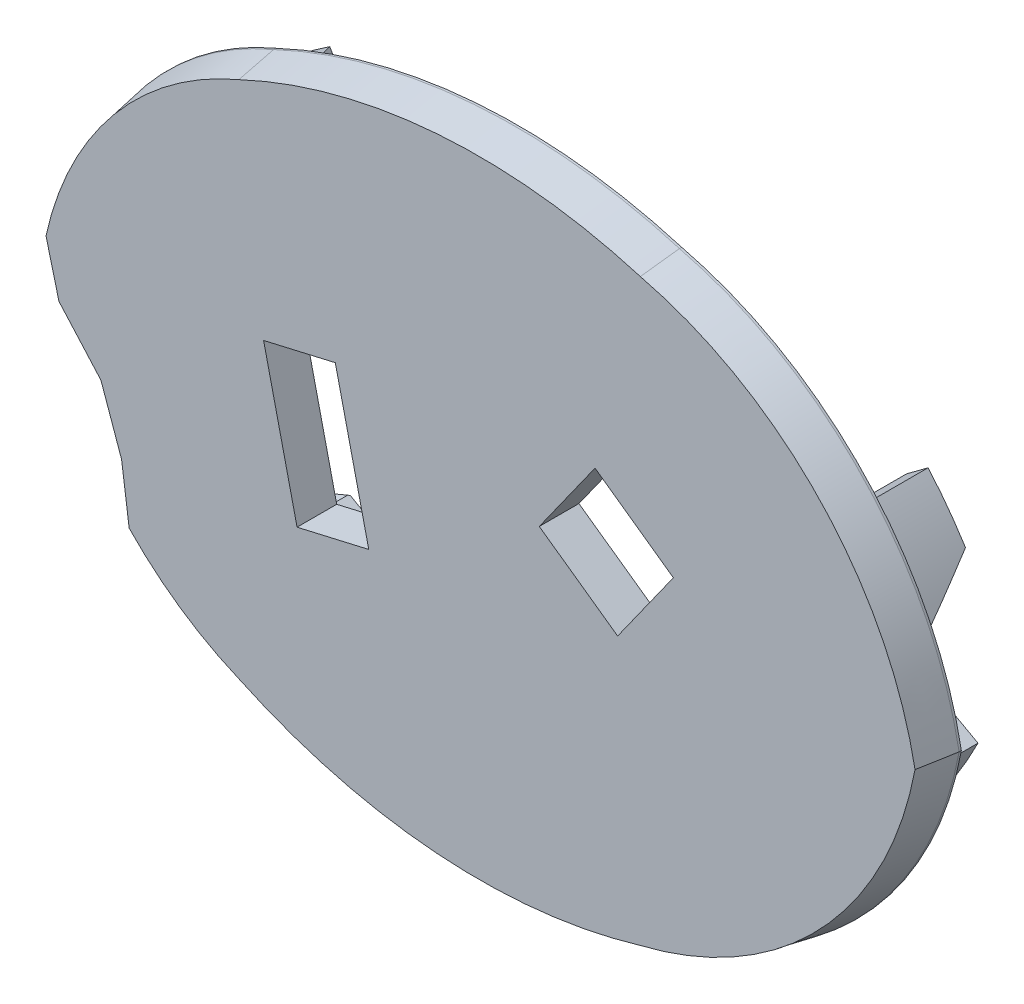
SolidWorks part; units mm, degrees
ref_plane "Ön Düzlem" through (0, 0, 0) normal (0, 0, 1) x (1, 0, 0)
ref_plane "Üst Düzlem" through (0, 0, 0) normal (0, 1, 0) x (1, 0, 0)
ref_plane "Sağ Düzlem" through (0, 0, 0) normal (1, 0, 0) x (0, 0, -1)
sketch "Çizim1" plane through (0, 0, 0) normal (0, 0, 1) x (1, 0, 0)
  line L2 (-58.677, -17.6893) -> (-56.8396, -24.8216)
  line L3 (-56.8396, -24.8216) -> (-51.1973, -31.1692)
  line L8 (-51.1973, -31.1692) -> (-48.5261, -38.7135)
  line L9 (-48.5261, -38.7135) -> (-47.4867, -46.3583)
  arc A1 (59.3086, -21.378) -> (21.9184, 18.1981) centre (10.0775, -30.4393) ccw
  arc A2 (21.9184, 18.1981) -> (-32.3459, 14.1122) centre (0.1322, -54.8435) ccw
  arc A5 (-32.3459, 14.1122) -> (-58.677, -17.6893) centre (-14.9778, -27.0699) ccw
  arc A6 (-32.3459, -56.8682) -> (-47.4867, -46.3583) centre (-14.9778, -15.6861) cw
  arc A9 (21.9184, -60.9541) -> (-32.3459, -56.8682) centre (0.1322, 12.0875) cw
  arc A10 (59.3086, -21.378) -> (21.9184, -60.9541) centre (10.0775, -12.3167) cw
extrude "Yükseklik-Ekstrüzyon1" add sketch "Çizim1" along normal blind 5.3
chamfer "Pah1" distance 5 angle 10 10 edges at (46.4645, 3.9379, 5.3) (46.4645, -46.6939, 5.3) (-5.5908, -63.9188, 5.3) (-40.464, -52.4022, 5.3) (-48.0064, -42.5359, 5.3) (-49.8617, -34.9414, 5.3) (-54.0184, -27.9954, 5.3) (-57.7583, -21.2554, 5.3) (-49.4036, 1.4341, 5.3) (-5.5908, 21.1628, 5.3) first distance on face at (43.539, 1.174, 2.65) first distance on face at (43.539, -43.93, 2.65) first distance on face at (-5.4023, -61.415, 2.65) first distance on face at (-40.1901, -52.0077, 2.65) first distance on face at (-48.0064, -42.5359, 2.65) first distance on face at (-49.8617, -34.9414, 2.65) first distance on face at (-54.0184, -27.9954, 2.65) first distance on face at (-57.7583, -21.2554, 2.65) first distance on face at (-47.4575, -0.1772, 2.65) first distance on face at (-5.4023, 18.659, 2.65)
sketch "Çizim2" plane through (0, 0, 0) normal (0, 0, -1) x (-1, 0, 0)
  line L0 (31.2763, 9.847) -> (27.7371, 3.911)
  line L1 (42.8096, -9.0722) -> (46.8763, -3.3933)
  line L2 (26.6903, -46.7388) -> (31.033, -53.1744)
  line L3 (39.0108, -42.3852) -> (40.3977, -36.6901)
  line L4 (40.3977, -36.6901) -> (43.5033, -30.0469)
  line L5 (43.5033, -30.0469) -> (48.6913, -24.7392)
  line L6 (48.6913, -24.7392) -> (53.3702, -18.2488)
  line L7 (-19.9716, 14.4087) -> (-19.195, 12.4343)
  line L8 (-41.465, -3.5137) -> (-44.3634, -1.352)
  line L9 (-45.3665, -26.7852) -> (-51.0307, -29.9037)
  line L10 (-32.8861, -43.1983) -> (-37.8394, -47.3322)
  line L11 (-44.8646, -9.307) -> (-41.465, -3.5137)
  line L17 (39.0108, -42.3852) -> (33.018, -43.1064)
  line L18 (33.018, -43.1064) -> (26.6903, -46.7388)
  line L25 (43.1871, -44.3376) -> (39.0108, -42.3852)
  line L27 (-49.2008, -15.6464) -> (-52.2554, -13.4137)
  line L29 (-41.465, -3.5137) -> (-44.8646, -9.307)
  line L30 (9.7339, 13.9491) -> (10.6003, 16.4649)
  line L31 (-4.7237, 14.7755) -> (-4.8826, 17.1405)
  line L32 (-32.8861, -43.1983) -> (-30.0976, -48.4438)
  line L33 (-44.8646, -9.307) -> (-49.2008, -15.6464)
  line L34 (44.1329, -37.3808) -> (43.1871, -44.3376)
  line L35 (46.5637, -30.5155) -> (44.1329, -37.3808)
  line L36 (51.6981, -24.7392) -> (46.5637, -30.5155)
  line L37 (53.3702, -18.2488) -> (51.6981, -24.7392)
  line L38 (-30.0976, -48.4438) -> (-23.4247, -52.0591)
  line L39 (-23.4247, -52.0591) -> (-27.6572, -54.775)
  arc A0 (27.7371, 3.911) -> (42.8096, -9.0722) centre (19.0626, -21.4001) cw
  arc A1 (-4.7237, 14.7755) -> (9.7339, 13.9491) centre (-0.0333, -30.0469) cw
  arc A2 (-45.3665, -26.7852) -> (-32.8861, -43.1983) centre (-10.9062, -13.5335) ccw
  arc A3 (-19.195, 12.4343) -> (-42.9142, -2.4329) centre (-9.1765, -29.9037) ccw
  arc A16 (-51.0307, -29.9037) -> (-27.6572, -54.775) centre (2.0709, -3.4186) ccw
  arc A17 (31.033, -53.1744) -> (43.1871, -44.3376) centre (13.6039, -16.4259) ccw
  arc A19 (46.8763, -3.3933) -> (31.2763, 9.847) centre (13.6039, -26.7852) ccw
  arc A20 (10.6003, 16.4649) -> (-4.8826, 17.1405) centre (-0.1461, -52.0591) ccw
  arc A21 (-19.9716, 14.4087) -> (-52.2554, -13.4137) centre (-4.7724, -35.8691) ccw
  point P22 (-27.193, -54.215)
  point P23 (0, 0)
  point P24 (-51.1377, -29.106)
  point P25 (-30.0976, -48.4438)
  point P26 (-23.4247, -52.0591)
  point P27 (0, 0)
  point P31 (-51.9148, -29.2561)
  point P32 (-27.6572, -54.775)
  point P33 (-44.8646, -28.2773)
  point P34 (0, 0)
  point P35 (-48.8981, -14.0339)
  point P39 (-51.3275, -13.0933)
  point P40 (-51.3275, -29.9574)
  point P41 (-45.3665, -26.7852)
  point P48 (-52.666, -12.862)
  point P49 (-49.0218, -15.3849)
  point P50 (-37.8394, -47.3322)
  point P51 (0, 0)
  point P52 (-51.9498, -12.7785)
  point P53 (0, 0)
  point P54 (-51.0307, -29.9037)
extrude "Yükseklik-Ekstrüzyon2" add sketch "Çizim2" along normal blind 10.5 contours L1 A19 L0 A0 | L8 A21 L27 L33 L11 | L9 A16 L10 A2 | L2 A17 L25 L17 L18 region at (-37.7924, 1.217, 0) region at (-34.4304, -46.9883, 0) region at (46.9316, -8.4558, 0) region at (42.4749, -37.2926, 0)
ref_plane "Düzlem1" through (0, 0, -2.5) normal (0, 0, -1) x (-1, 0, 0)
sketch "Çizim4" plane through (0, 0, -2.5) normal (0, 0, -1) x (-1, 0, 0)
  line L0 (-32.8861, -43.1983) -> (-37.8394, -47.3322) construction
  line L1 (-19.9716, 14.4087) -> (-19.195, 12.4343) construction
  line L2 (-49.2008, -15.6464) -> (-52.2554, -13.4137) construction
  line L3 (-44.8646, -9.307) -> (-49.2008, -15.6464) construction
  line L4 (-44.8646, -9.307) -> (-41.465, -3.5137) construction
  line L5 (-41.465, -3.5137) -> (-44.8646, -9.307) construction
  line L6 (-41.465, -3.5137) -> (-44.3634, -1.352) construction
  line L7 (43.1871, -44.3376) -> (39.0108, -42.3852) construction
  line L8 (31.2763, 9.847) -> (27.7371, 3.911) construction
  line L9 (42.8096, -9.0722) -> (46.8763, -3.3933) construction
  line L10 (39.0108, -42.3852) -> (40.3977, -36.6901) construction
  line L11 (40.3977, -36.6901) -> (43.5033, -30.0469) construction
  line L12 (43.5033, -30.0469) -> (48.6913, -24.7392) construction
  line L13 (48.6913, -24.7392) -> (53.3702, -18.2488) construction
  line L14 (53.3702, -18.2488) -> (51.6981, -24.7392) construction
  line L15 (51.6981, -24.7392) -> (46.5637, -30.5155) construction
  line L16 (46.5637, -30.5155) -> (44.1329, -37.3808) construction
  line L17 (44.1329, -37.3808) -> (43.1871, -44.3376) construction
  line L18 (26.6903, -46.7388) -> (31.033, -53.1744) construction
  line L19 (33.018, -43.1064) -> (26.6903, -46.7388) construction
  line L20 (39.0108, -42.3852) -> (33.018, -43.1064) construction
  line L21 (9.7339, 13.9491) -> (10.6003, 16.4649) construction
  line L22 (-4.7237, 14.7755) -> (-4.8826, 17.1405) construction
  line L23 (-32.8861, -43.1983) -> (-30.0976, -48.4438) construction
  line L24 (-30.0976, -48.4438) -> (-23.4247, -52.0591) construction
  line L25 (-23.4247, -52.0591) -> (-27.6572, -54.775) construction
  line L26 (-45.3665, -26.7852) -> (-51.0307, -29.9037) construction
  line L27 (-32.8861, -43.1983) -> (-37.8394, -47.3322)
  line L28 (-19.9716, 14.4087) -> (-19.195, 12.4343)
  line L29 (-49.2008, -15.6464) -> (-52.2554, -13.4137)
  line L30 (-44.8646, -9.307) -> (-49.2008, -15.6464)
  line L31 (-44.8646, -9.307) -> (-41.465, -3.5137)
  line L32 (-41.465, -3.5137) -> (-44.8646, -9.307)
  line L33 (-41.465, -3.5137) -> (-44.3634, -1.352)
  line L34 (43.1871, -44.3376) -> (39.0108, -42.3852)
  line L35 (31.2763, 9.847) -> (27.7371, 3.911)
  line L36 (42.8096, -9.0722) -> (46.8763, -3.3933)
  line L37 (39.0108, -42.3852) -> (40.3977, -36.6901)
  line L38 (40.3977, -36.6901) -> (43.5033, -30.0469)
  line L39 (43.5033, -30.0469) -> (48.6913, -24.7392)
  line L40 (48.6913, -24.7392) -> (53.3702, -18.2488)
  line L41 (53.3702, -18.2488) -> (51.6981, -24.7392)
  line L42 (51.6981, -24.7392) -> (46.5637, -30.5155)
  line L43 (46.5637, -30.5155) -> (44.1329, -37.3808)
  line L44 (44.1329, -37.3808) -> (43.1871, -44.3376)
  line L45 (26.6903, -46.7388) -> (31.033, -53.1744)
  line L46 (33.018, -43.1064) -> (26.6903, -46.7388)
  line L47 (39.0108, -42.3852) -> (33.018, -43.1064)
  line L48 (9.7339, 13.9491) -> (10.6003, 16.4649)
  line L49 (-4.7237, 14.7755) -> (-4.8826, 17.1405)
  line L50 (-32.8861, -43.1983) -> (-30.0976, -48.4438)
  line L51 (-30.0976, -48.4438) -> (-23.4247, -52.0591)
  line L52 (-23.4247, -52.0591) -> (-27.6572, -54.775)
  line L53 (-45.3665, -26.7852) -> (-51.0307, -29.9037)
  arc A0 (-19.195, 12.4343) -> (-42.9142, -2.4329) centre (-9.1765, -29.9037) ccw construction
  arc A1 (-19.9716, 14.4087) -> (-52.2554, -13.4137) centre (-4.7724, -35.8691) ccw construction
  arc A2 (42.8096, -9.0722) -> (27.7371, 3.911) centre (19.0626, -21.4001) ccw construction
  arc A3 (46.8763, -3.3933) -> (31.2763, 9.847) centre (13.6039, -26.7852) ccw construction
  arc A4 (31.033, -53.1744) -> (43.1871, -44.3376) centre (13.6039, -16.4259) ccw construction
  arc A5 (10.6003, 16.4649) -> (-4.8826, 17.1405) centre (-0.1461, -52.0591) ccw construction
  arc A6 (9.7339, 13.9491) -> (-4.7237, 14.7755) centre (-0.0333, -30.0469) ccw construction
  arc A7 (-51.0307, -29.9037) -> (-27.6572, -54.775) centre (2.0709, -3.4186) ccw construction
  arc A8 (-45.3665, -26.7852) -> (-32.8861, -43.1983) centre (-10.9062, -13.5335) ccw construction
  arc A9 (-19.195, 12.4343) -> (-42.9142, -2.4329) centre (-9.1765, -29.9037) ccw
  arc A10 (-19.9716, 14.4087) -> (-52.2554, -13.4137) centre (-4.7724, -35.8691) ccw
  arc A11 (42.8096, -9.0722) -> (27.7371, 3.911) centre (19.0626, -21.4001) ccw
  arc A12 (46.8763, -3.3933) -> (31.2763, 9.847) centre (13.6039, -26.7852) ccw
  arc A13 (31.033, -53.1744) -> (43.1871, -44.3376) centre (13.6039, -16.4259) ccw
  arc A14 (10.6003, 16.4649) -> (-4.8826, 17.1405) centre (-0.1461, -52.0591) ccw
  arc A15 (9.7339, 13.9491) -> (-4.7237, 14.7755) centre (-0.0333, -30.0469) ccw
  arc A16 (-51.0307, -29.9037) -> (-27.6572, -54.775) centre (2.0709, -3.4186) ccw
  arc A17 (-45.3665, -26.7852) -> (-32.8861, -43.1983) centre (-10.9062, -13.5335) ccw
extrude "Yükseklik-Ekstrüzyon3" add sketch "Çizim4" against normal up to surface (2.5 mm away) contours L28 A10 L33 A9 | A15 L48 A14 L49 | L44 L43 L42 L41 L40 L39 L38 L37 L34 | L27 A16 L52 L51 L50 region at (31.1342, -49.4794, -2.5) region at (32.0171, 7.1873, -2.5) region at (-44.8221, -33.1734, -2.5) region at (-2.8392, 15.9234, -2.5) up to face at (46.513, -8.5922, 0)
chamfer "Pah4" distance 6 angle 55 1 edges at (50.7281, -14.5301, -10.5) first distance on face at (46.513, -8.5922, -10.5)
chamfer "Pah5" distance 6 angle 53 1 edges at (35.3627, -45.2653, -10.5) first distance on face at (42.2753, -37.1802, -10.5)
chamfer "Pah8" distance 5 angle 60 1 edges at (-29.5067, 6.879, -10.5) first distance on face at (-37.6992, 0.9356, -10.5)
sketch "Çizim5" plane through (0, 0, -10.5) normal (0, 0, -1) x (-1, 0, 0)
  line L0 (43.1871, -44.3376) -> (39.4463, -40.5968)
  line L1 (39.0108, -42.3852) -> (39.4463, -40.5968)
  line L3 (39.0108, -42.3852) -> (43.1871, -44.3376)
extrude "Yükseklik-Ekstrüzyon4" add sketch "Çizim5" against normal blind 10.5
chamfer "Pah10" distance 6.5 angle 50 1 edges at (-41.3167, -42.4672, -10.5) first distance on face at (-35.4662, -45.1509, -10.5)
sketch "Çizim6" plane through (0, 0, 0) normal (0, 0, -1) x (-1, 0, 0)
  line L0 (-26.105, -15.3171) -> (-15.6301, -7.8656)
  line L1 (24.2046, -34.6186) -> (28.68, -15.2336)
  line L2 (24.2046, -34.6186) -> (14.6201, -32.4059)
  line L3 (14.6201, -32.4059) -> (19.0955, -13.0208)
  line L4 (28.68, -15.2336) -> (19.0955, -13.0208)
  line L5 (-15.6301, -7.8656) -> (-8.1786, -18.3405)
  line L6 (-8.1786, -18.3405) -> (-18.6535, -25.7921)
  line L7 (-18.6535, -25.7921) -> (-26.105, -15.3171)
extrude "Kes-Ekstrüzyon1" cut sketch "Çizim6" against normal blind 10.5
sketch "Sketch1" plane through (0, 0, -2.5) normal (0, 0, -1) x (-1, 0, 0)
  line L0 (50.3913, -22.381) -> (52.0058, -23.5449)
  line L9 (39.4463, -40.5968) -> (43.1871, -44.3376)
  line L10 (43.1871, -44.3376) -> (44.1329, -37.3808)
  line L11 (44.1329, -37.3808) -> (46.5637, -30.5155)
  line L12 (46.5637, -30.5155) -> (51.6981, -24.7392)
  line L13 (51.6981, -24.7392) -> (53.3702, -18.2488)
  line L14 (53.3702, -18.2488) -> (48.6913, -24.7392)
  line L15 (48.6913, -24.7392) -> (43.5033, -30.0469)
  line L16 (43.5033, -30.0469) -> (40.3977, -36.6901)
  line L17 (40.3977, -36.6901) -> (39.4463, -40.5968)
  line L18 (39.4463, -40.5968) -> (43.1871, -44.3376)
  line L22 (52.0058, -23.5449) -> (53.3702, -18.2488)
  line L23 (53.3702, -18.2488) -> (50.3913, -22.381)
  line M14 (51.6981, -24.7392) -> (53.3702, -18.2488)
  line M15 (53.3702, -18.2488) -> (48.6913, -24.7392)
  dimension "D1" = 0
extrude "Cut-Extrude1" cut sketch "Sketch1" against normal up to surface (2.5 mm away) contours L0 M15 M14 | L22 L23 L0 region at (-51.9225, -21.3916, -2.5) up to face at (17.1418, -16.8288, 0)
sketch "Sketch2" plane through (0, 0, -2.5) normal (0, 0, -1) x (-1, 0, 0)
  line L0 (49.252, -23.9614) -> (50.5718, -26.4287)
  line L2 (48.6913, -24.7392) -> (50.3913, -22.381) construction
  line L3 (50.5718, -26.4287) -> (55.4064, -23.8427)
  line L4 (55.4064, -23.8427) -> (51.2159, -16.0084)
  line L5 (51.2159, -16.0084) -> (49.252, -23.9614)
  point P2 (54.7451, -24.1965)
  point P7 (0, 0)
  dimension "D1" = 1.75
extrude "Cut-Extrude2" cut sketch "Sketch2" against normal up to surface (2.5 mm away) up to face at (-42.3642, -35.4113, 0)
